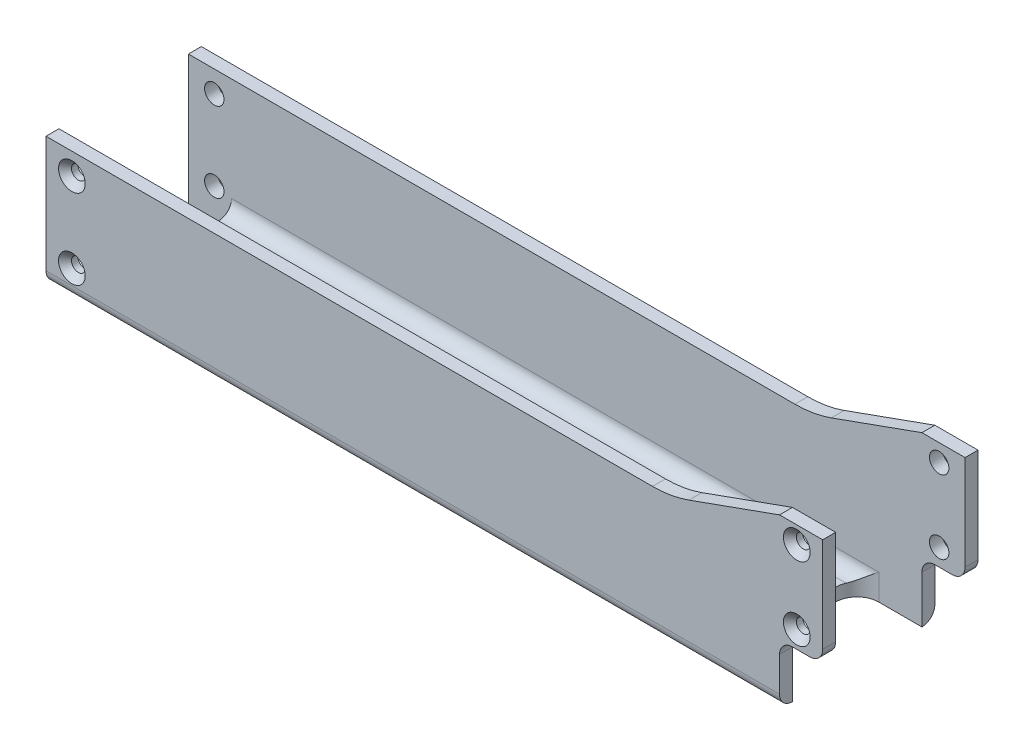
SolidWorks part; units mm, degrees
ref_plane "Front Plane" through (0, 0, 0) normal (0, 0, 1) x (1, 0, 0)
ref_plane "Top Plane" through (0, 0, 0) normal (0, 1, 0) x (1, 0, 0)
ref_plane "Right Plane" through (0, 0, 0) normal (1, 0, 0) x (0, 0, -1)
sketch "Sketch1" plane through (0, 0, 0) normal (0, 0, 1) x (1, 0, 0)
  line L0 (52.7874, 245.1803) -> (193.3525, 245.1803)
  line L4 (52.7874, 245.1803) -> (52.7874, 215.1803)
  line L5 (52.7874, 215.1803) -> (222.7874, 215.1803)
  line L6 (222.7874, 245.1803) -> (222.7874, 215.1803) construction
  line L7 (222.7874, 215.1803) -> (222.7874, 254.1811)
  line L8 (222.7874, 254.1811) -> (201.7956, 246.6492)
  line L9 (241.0832, 254.1811) -> (222.7874, 254.1811) construction
  arc A0 (201.7956, 246.6492) -> (193.3525, 245.1803) centre (193.3525, 270.1803) cw
extrude "Boss-Extrude1" add sketch "Sketch1" against normal blind 3
sketch "Sketch3" plane through (0, 0, -36) normal (0, 0, -1) x (-1, 0, 0)
  line L4 (-222.7874, 254.1811) -> (-222.7874, 215.1803)
  line L5 (-222.7874, 254.1811) -> (-222.7874, 215.1803)
  line L6 (-52.7874, 215.1803) -> (-52.7874, 245.1803)
  line L7 (-52.7874, 245.1803) -> (-193.3525, 245.1803)
  line L9 (-201.7956, 246.6492) -> (-222.7874, 254.1811)
  line L10 (-201.7956, 246.6492) -> (-222.7874, 254.1811)
  line L11 (-222.7874, 215.1803) -> (-52.7874, 215.1803)
  line L12 (-52.7874, 215.1803) -> (-52.7874, 245.1803)
  line L13 (-52.7874, 245.1803) -> (-193.3525, 245.1803)
  line L17 (-222.7874, 215.1803) -> (-52.7874, 215.1803)
  arc A1 (-201.7956, 246.6492) -> (-193.3525, 245.1803) centre (-193.3525, 270.1803) ccw
  arc A2 (-201.7956, 246.6492) -> (-193.3525, 245.1803) centre (-193.3525, 270.1803) ccw
  dimension "D1" = 0
extrude "Boss-Extrude2" add sketch "Sketch3" against normal blind 3 separate body
sketch "Sketch4" plane through (0, 0, -3) normal (0, 0, -1) x (-1, 0, 0)
  line L1 (-52.7874, 215.1803) -> (-207.7874, 215.1803)
  line L2 (-52.7874, 215.1803) -> (-52.7874, 218.1803)
  line L3 (-52.7874, 218.1803) -> (-207.7874, 218.1803)
  line L4 (-207.7874, 215.1803) -> (-207.7874, 218.1803)
extrude "Boss-Extrude3" add sketch "Sketch4" along normal up to surface (30 mm away) up to face at (157.7268, 236.8645, -33)
fillet "Fillet1" radius 5 2 edges at (207.7874, 216.6803, -33) (207.7874, 216.6803, -3)
ref_plane "Plane1" through (130.2874, 0, 0) normal (1, 0, 0) x (0, 0, -1)
fillet "Fillet2" radius 3 4 edges at (132.7874, 218.1803, -3) (132.7874, 218.1803, -33) (137.7874, 215.1803, 0) (137.7874, 215.1803, -36)
sketch "Sketch5" plane through (0, 218.1803, 0) normal (0, 1, 0) x (1, 0, 0)
  line L0 (52.7874, 33) -> (193.3525, 33) construction
  line L1 (52.7874, 3) -> (62.7874, 3)
  line L2 (52.7874, 3) -> (52.7874, 33)
  line L3 (52.7874, 33) -> (62.7874, 33)
  line L4 (62.7874, 3) -> (62.7874, 33)
extrude "Cut-Extrude1" cut sketch "Sketch5" against normal through all both and the other way through all
sketch "Sketch6" plane through (0, 0, 0) normal (0, 0, 1) x (1, 0, 0)
  line L0 (62.7877, 245.1806) -> (62.7877, 215.1806) construction
  line L1 (54.7876, 222.1805) -> (54.7876, 245.1805) construction
  line L2 (62.7877, 245.1806) -> (62.7877, 215.1806) construction
  line L3 (54.7876, 222.1805) -> (54.7876, 245.1805) construction
  line L4 (54.7876, 245.1805) -> (62.7877, 245.1806) construction
  line L5 (58.7876, 245.1805) -> (58.7876, 215.1803) construction
  line L6 (52.7874, 215.1803) -> (62.7874, 215.1803) construction
  circle A0 centre (58.7876, 240.1805) radius 1.6
  circle A1 centre (58.7876, 221.6803) radius 1.6
extrude "Cut-Extrude2" cut sketch "Sketch6" against normal blind 4
sketch "Sketch7" plane through (222.7874, 0, 0) normal (1, 0, 0) x (0, 0, -1)
  line L0 (0, 218.1803) -> (0, 254.1811) construction
  line L1 (3, 254.1811) -> (0, 254.1811)
  line L2 (3, 254.1811) -> (3, 229.1811)
  line L3 (3, 229.1811) -> (0, 229.1811)
  line L4 (0, 254.1811) -> (0, 229.1811)
  line L5 (36, 254.1811) -> (36, 218.1803) construction
  line L6 (33, 254.1811) -> (36, 254.1811)
  line L7 (33, 254.1811) -> (33, 229.1811)
  line L8 (33, 229.1811) -> (36, 229.1811)
  line L9 (36, 254.1811) -> (36, 229.1811)
extrude "Boss-Extrude4" add sketch "Sketch7" along normal blind 10
fillet "Fillet3" radius 3 4 edges at (222.7874, 229.1811, -34.5) (222.7874, 229.1811, -1.5) (232.7874, 229.1811, -34.5) (232.7874, 229.1811, -1.5)
sketch "Sketch9" plane through (0, 0, 0) normal (0, 0, 1) x (1, 0, 0)
  line L0 (230.7874, 254.1811) -> (230.7874, 229.3173) construction
  line L1 (230.7874, 254.1811) -> (230.7874, 229.3173) construction
  line L2 (222.7874, 226.1811) -> (222.7874, 254.1811) construction
  line L3 (222.7874, 226.1811) -> (222.7874, 254.1811) construction
  line L4 (222.7874, 254.1811) -> (230.7874, 254.1811) construction
  line L5 (226.7874, 254.1811) -> (226.7874, 229.1811) construction
  circle A0 centre (226.7874, 250.1811) radius 1.6
  circle A1 centre (226.7874, 233.1811) radius 1.6
extrude "Cut-Extrude3" cut sketch "Sketch9" against normal blind 5
sketch "Sketch10" plane through (0, 0, -36) normal (0, 0, -1) x (-1, 0, 0)
  circle A0 centre (-226.7874, 250.1811) radius 2.25
  circle A1 centre (-226.7874, 233.1811) radius 2.25
  circle A2 centre (-58.7876, 240.1805) radius 2.25
  circle A3 centre (-58.7876, 221.6803) radius 2.25
extrude "Cut-Extrude4" cut sketch "Sketch10" against normal blind 3
chamfer "Chamfer1" distance 1.5 angle 45 4 edges at (60.3876, 240.1805, 0) (60.3876, 221.6803, 0) (228.3874, 250.1811, 0) (228.3874, 233.1811, 0)
